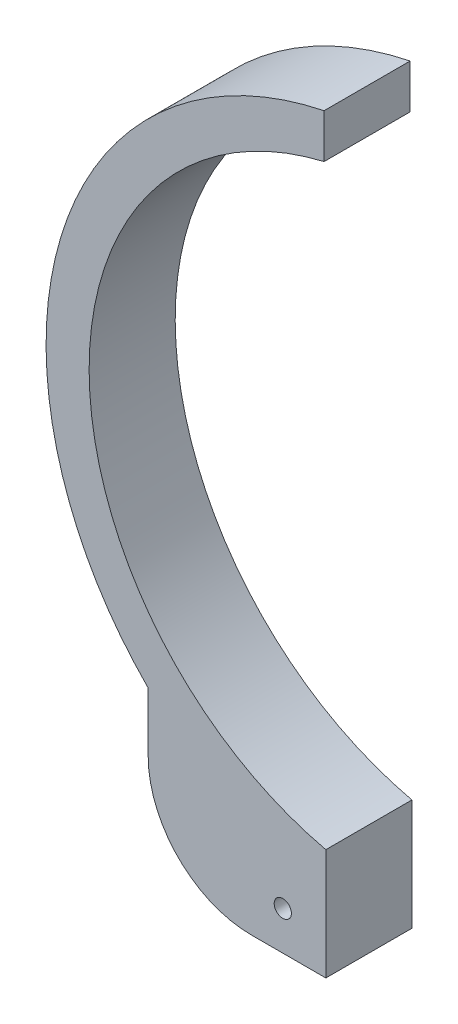
SolidWorks part; units mm, degrees
ref_plane "Front Plane" through (0, 0, 0) normal (0, 0, 1) x (1, 0, 0)
ref_plane "Top Plane" through (0, 0, 0) normal (0, 1, 0) x (1, 0, 0)
ref_plane "Right Plane" through (0, 0, 0) normal (1, 0, 0) x (0, 0, -1)
sketch "Sketch1" plane through (0, 0, 0) normal (0, 0, 1) x (1, 0, 0)
  line L0 (0, -35.5) -> (0, 35.5)
  line L1 (0, 35.5) -> (0, 40.5)
  line L2 (0, 40.5) -> (0, -40.5)
  line L3 (-28.6378, -28.6378) -> (-28.6378, -40.5)
  line L4 (-28.6378, -40.5) -> (0, -40.5)
  line L5 (-0.6378, -40.5) -> (-0.6378, -35.4943)
  line L6 (-3.6378, -40.5) -> (-3.6378, -35.3131)
  line L7 (-3.6378, -40.5) -> (-3.6378, -47.5)
  line L8 (-28.6378, -40.5) -> (0, -40.5)
  line L9 (-28.6378, -40.5) -> (-28.6378, -35.5)
  line L10 (-16.6378, -47.5) -> (0, -47.5)
  line L11 (0, -40.5) -> (0, -47.5)
  line L12 (-8, -34.5868) -> (-8, -47.5)
  line L13 (-13, -38.3569) -> (-13, -47.5)
  circle A0 centre (0, 0) radius 35.5
  circle A1 centre (0, 0) radius 40.5
  arc A2 (-40.5, 0) -> (0, -40.5) centre (0, 0) ccw
  arc A3 (-28.6378, -28.6378) -> (0, -40.5) centre (0, 0) ccw
  arc A4 (-28.6378, -35.5) -> (-16.6378, -47.5) centre (-16.6378, -35.5) ccw
  circle A5 centre (-13, -42.9999) radius 1
  point P27 (-28.6378, -47.5)
  dimension "D1" = 71
  dimension "D4" = 28
  dimension "D5" = 2
  dimension "D8" = 5
  dimension "D9" = 7
  dimension "D11" = 12
  dimension "D2" = 5
  dimension "D3" = 5
  dimension "D6" = 13
  dimension "D7" = 25
  dimension "D10" = 4.643
extrude "Boss-Extrude1" add sketch "Sketch1" along normal blind 10 contours A1 L3 L4 | A1 L2 A0 L1 | A5 L4 L12 A1 L13 | A5 L4 L9 L10 L13 | A5 L13 L10 L12 L4 region at (-36.1637, 4.1279, 0) region at (-10.8962, -39.7398, 0) region at (-22.7388, -36.7388, 0) region at (-10.4025, -44.047, 0) region at (-19.1204, -43.5911, 0)
sketch "Sketch2" plane through (0, 0, 10) normal (0, 0, 1) x (1, 0, 0)
  line L1 (0, 40.5) -> (-8.204, 40.5)
  line L2 (0, 40.5) -> (0, 31.1468)
  line L3 (0, 31.1468) -> (-8.204, 31.1468)
  line L4 (-8.204, 40.5) -> (-8.204, 31.1468)
extrude "Cut-Extrude1" cut sketch "Sketch2" against normal blind 10
